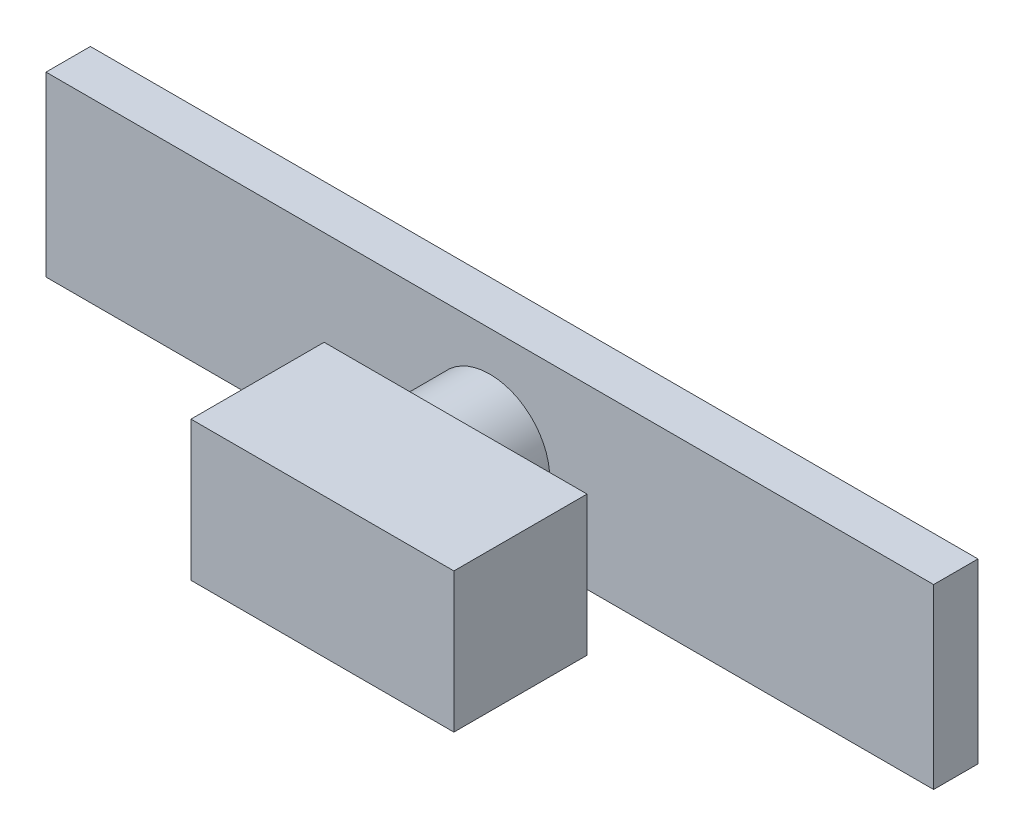
SolidWorks part; units mm, degrees
ref_plane "Front Plane" through (0, 0, 0) normal (0, 0, 1) x (1, 0, 0)
ref_plane "Top Plane" through (0, 0, 0) normal (0, 1, 0) x (1, 0, 0)
ref_plane "Right Plane" through (0, 0, 0) normal (1, 0, 0) x (0, 0, -1)
sketch "Sketch2" plane through (0, 0, 0) normal (0, 0, 1) x (1, 0, 0)
  line L1 (-47.8692, 21.2481) -> (206.1308, 21.2481)
  line L2 (-47.8692, 21.2481) -> (-47.8692, 8.5481)
  line L3 (-47.8692, 8.5481) -> (206.1308, 8.5481)
  line L4 (206.1308, 21.2481) -> (206.1308, 8.5481)
  dimension "D1" = 12.7
  dimension "D2" = 254
extrude "Boss-Extrude1" add sketch "Sketch2" along normal blind 50.8
sketch "Sketch3" plane through (0, 21.2481, 0) normal (0, 1, 0) x (1, 0, 0)
  circle A0 centre (79.1308, -28.4831) radius 17.1408
extrude "Boss-Extrude2" add sketch "Sketch3" along normal blind 19.05
sketch "Sketch4" plane through (0, 40.2981, 0) normal (0, 1, 0) x (1, 0, 0)
  line L1 (50.7675, -8.111) -> (126.0034, -8.111)
  line L2 (50.7675, -8.111) -> (50.7675, -48.0661)
  line L3 (50.7675, -48.0661) -> (126.0034, -48.0661)
  line L4 (126.0034, -8.111) -> (126.0034, -48.0661)
extrude "Boss-Extrude3" add sketch "Sketch4" along normal blind 38.1
scale "Scale2" scale about centroid uniform scaling yes scale factor 0.06
move or copy body "rotate" bodies to move or copy 105 copy no rotation origin (0, 33.6669, 26.5501) rotation axis (1, 0, 0) rotation angle 90
scale "Scale5" scale about centroid uniform scaling yes scale factor 0.25
move or copy body "-4 x" bodies to move or copy 111 copy no translate (-101.6, 0, 0)
move or copy body "-2 y" bodies to move or copy 117 copy no translate (0, -50.8, 0)
scale "Scale6" bodies to scale 121 scale about centroid uniform scaling yes scale factor 0.25
